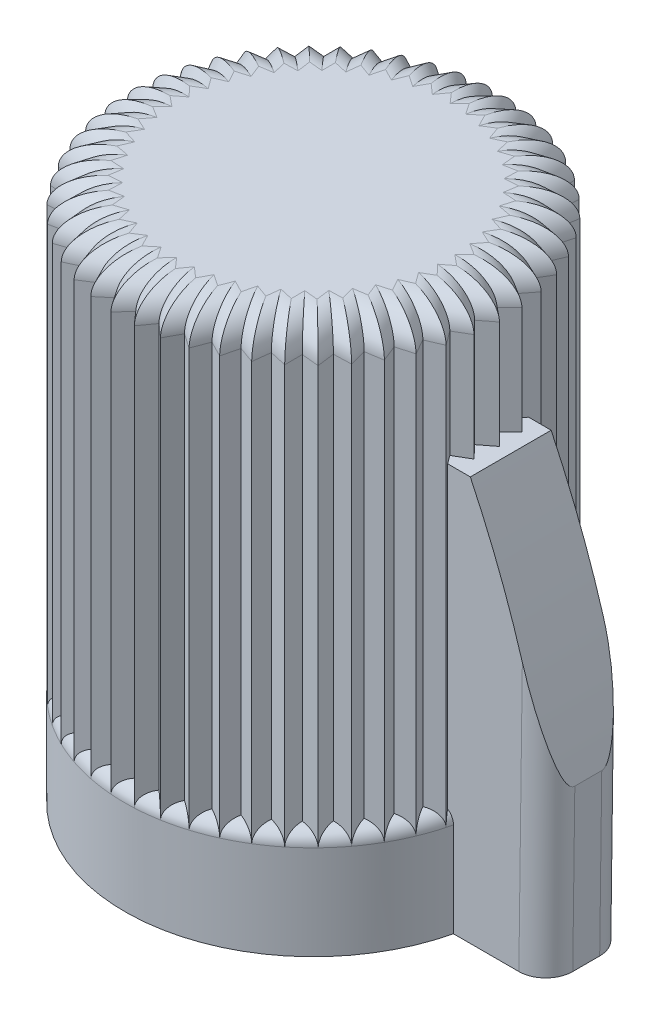
SolidWorks part; units mm, degrees
ref_plane "Спереди" through (0, 0, 0) normal (0, 0, 1) x (1, 0, 0)
ref_plane "Сверху" through (0, 0, 0) normal (0, 1, 0) x (1, 0, 0)
ref_plane "Справа" through (0, 0, 0) normal (1, 0, 0) x (0, 0, -1)
sketch "Sketch1" plane through (0, 0, 0) normal (0, 1, 0) x (1, 0, 0)
  circle A0 centre (0, 0) radius 7
  dimension "D1" = 14
extrude "Boss-Extrude1" add sketch "Sketch1" along normal blind 20
sketch "Sketch2" plane through (0, 0, 0) normal (0, -1, 0) x (1, 0, 0)
  circle A0 centre (0, 0) radius 3.125
  dimension "D1" = 6.25
extrude "Cut-Extrude1" cut sketch "Sketch2" against normal blind 17
sketch "Sketch3" plane through (0, 0, 0) normal (0, -1, 0) x (1, 0, 0)
  circle A0 centre (0, 0) radius 6
  dimension "D1" = 12
extrude "Cut-Extrude2" cut sketch "Sketch3" against normal blind 4
sketch "Sketch4" plane through (0, 20, 0) normal (0, 1, 0) x (1, 0, 0)
  line L0 (6.3681, -1.303) -> (6.7563, -1.8311)
  line L1 (6.7563, -1.8311) -> (6.1545, -2.0909)
  line L2 (6.1545, -2.0909) -> (6.4735, -2.6634)
  line L3 (6.4735, -2.6634) -> (5.8439, -2.8458)
  line L4 (5.8439, -2.8458) -> (6.0886, -3.4538)
  line L5 (6.0886, -3.4538) -> (5.4412, -3.5558)
  line L6 (5.4412, -3.5558) -> (5.6077, -4.1897)
  line L7 (5.6077, -4.1897) -> (4.9526, -4.2097)
  line L8 (4.9526, -4.2097) -> (5.0384, -4.8595)
  line L9 (5.0384, -4.8595) -> (4.386, -4.7972)
  line L10 (4.386, -4.7972) -> (4.3896, -5.4526)
  line L11 (4.3896, -5.4526) -> (3.7501, -5.3091)
  line L12 (3.7501, -5.3091) -> (3.6716, -5.9598)
  line L13 (3.6716, -5.9598) -> (3.0552, -5.7372)
  line L14 (3.0552, -5.7372) -> (2.8957, -6.373)
  line L15 (2.8957, -6.373) -> (2.312, -6.0749)
  line L16 (2.312, -6.0749) -> (2.0741, -6.6857)
  line L17 (2.0741, -6.6857) -> (1.5324, -6.3168)
  line L18 (1.5324, -6.3168) -> (1.2199, -6.8929)
  line L19 (1.2199, -6.8929) -> (0.7286, -6.459)
  line L20 (0.7286, -6.459) -> (0.3463, -6.9914)
  line L21 (0.3463, -6.9914) -> (-0.0867, -6.4994)
  line L22 (-0.0867, -6.4994) -> (-0.5327, -6.9797)
  line L23 (-0.5327, -6.9797) -> (-0.9006, -6.4373)
  line L24 (-0.9006, -6.4373) -> (-1.4033, -6.8579)
  line L25 (-1.4033, -6.8579) -> (-1.7003, -6.2737)
  line L26 (-1.7003, -6.2737) -> (-2.2517, -6.628)
  line L27 (-2.2517, -6.628) -> (-2.4732, -6.0111)
  line L28 (-2.4732, -6.0111) -> (-3.0647, -6.2935)
  line L29 (-3.0647, -6.2935) -> (-3.2071, -5.6537)
  line L30 (-3.2071, -5.6537) -> (-3.8293, -5.8597)
  line L31 (-3.8293, -5.8597) -> (-3.8904, -5.2072)
  line L32 (-3.8904, -5.2072) -> (-4.5335, -5.3336)
  line L33 (-4.5335, -5.3336) -> (-4.5124, -4.6785)
  line L34 (-4.5124, -4.6785) -> (-5.1662, -4.7234)
  line L35 (-5.1662, -4.7234) -> (-5.0631, -4.0761)
  line L36 (-5.0631, -4.0761) -> (-5.7175, -4.0386)
  line L37 (-5.7175, -4.0386) -> (-5.5341, -3.4094)
  line L38 (-5.5341, -3.4094) -> (-6.1786, -3.2902)
  line L39 (-6.1786, -3.2902) -> (-5.9178, -2.6889)
  line L40 (-5.9178, -2.6889) -> (-6.5422, -2.4898)
  line L41 (-6.5422, -2.4898) -> (-6.2081, -1.926)
  line L42 (-6.2081, -1.926) -> (-6.8027, -1.6503)
  line L43 (-6.8027, -1.6503) -> (-6.4005, -1.1327)
  line L44 (-6.4005, -1.1327) -> (-6.9559, -0.7846)
  line L45 (-6.9559, -0.7846) -> (-6.492, -0.3216)
  line L46 (-6.492, -0.3216) -> (-6.9994, 0.0934)
  line L47 (-6.9994, 0.0934) -> (-6.4812, 0.4946)
  line L48 (-6.4812, 0.4946) -> (-6.9325, 0.9699)
  line L49 (-6.9325, 0.9699) -> (-6.3681, 1.303)
  line L50 (-6.3681, 1.303) -> (-6.7563, 1.8311)
  line L51 (-6.7563, 1.8311) -> (-6.1545, 2.0909)
  line L52 (-6.1545, 2.0909) -> (-6.4735, 2.6634)
  line L53 (-6.4735, 2.6634) -> (-5.8439, 2.8458)
  line L54 (-5.8439, 2.8458) -> (-6.0886, 3.4538)
  line L55 (-6.0886, 3.4538) -> (-5.4412, 3.5558)
  line L56 (-5.4412, 3.5558) -> (-5.6077, 4.1897)
  line L57 (-5.6077, 4.1897) -> (-4.9526, 4.2097)
  line L58 (-4.9526, 4.2097) -> (-5.0384, 4.8595)
  line L59 (-5.0384, 4.8595) -> (-4.386, 4.7972)
  line L60 (-4.386, 4.7972) -> (-4.3896, 5.4526)
  line L61 (-4.3896, 5.4526) -> (-3.7501, 5.3091)
  line L62 (-3.7501, 5.3091) -> (-3.6716, 5.9598)
  line L63 (-3.6716, 5.9598) -> (-3.0552, 5.7372)
  line L64 (-3.0552, 5.7372) -> (-2.8957, 6.373)
  line L65 (-2.8957, 6.373) -> (-2.312, 6.0749)
  line L66 (-2.312, 6.0749) -> (-2.0741, 6.6857)
  line L67 (-2.0741, 6.6857) -> (-1.5324, 6.3168)
  line L68 (-1.5324, 6.3168) -> (-1.2199, 6.8929)
  line L69 (-1.2199, 6.8929) -> (-0.7286, 6.459)
  line L70 (-0.7286, 6.459) -> (-0.3463, 6.9914)
  line L71 (-0.3463, 6.9914) -> (0.0867, 6.4994)
  line L72 (0.0867, 6.4994) -> (0.5327, 6.9797)
  line L73 (0.5327, 6.9797) -> (0.9006, 6.4373)
  line L74 (0.9006, 6.4373) -> (1.4033, 6.8579)
  line L75 (1.4033, 6.8579) -> (1.7003, 6.2737)
  line L76 (1.7003, 6.2737) -> (2.2517, 6.628)
  line L77 (2.2517, 6.628) -> (2.4732, 6.0111)
  line L78 (2.4732, 6.0111) -> (3.0647, 6.2935)
  line L79 (3.0647, 6.2935) -> (3.2071, 5.6537)
  line L80 (3.2071, 5.6537) -> (3.8293, 5.8597)
  line L81 (3.8293, 5.8597) -> (3.8904, 5.2072)
  line L82 (3.8904, 5.2072) -> (4.5335, 5.3336)
  line L83 (4.5335, 5.3336) -> (4.5124, 4.6785)
  line L84 (4.5124, 4.6785) -> (5.1662, 4.7234)
  line L85 (5.1662, 4.7234) -> (5.0631, 4.0761)
  line L86 (5.0631, 4.0761) -> (5.7175, 4.0386)
  line L87 (5.7175, 4.0386) -> (5.5341, 3.4094)
  line L88 (5.5341, 3.4094) -> (6.1786, 3.2902)
  line L89 (6.1786, 3.2902) -> (5.9178, 2.6889)
  line L90 (5.9178, 2.6889) -> (6.5422, 2.4898)
  line L91 (6.5422, 2.4898) -> (6.2081, 1.926)
  line L92 (6.2081, 1.926) -> (6.8027, 1.6503)
  line L93 (6.8027, 1.6503) -> (6.4005, 1.1327)
  line L94 (6.4005, 1.1327) -> (6.9559, 0.7846)
  line L95 (6.9559, 0.7846) -> (6.492, 0.3216)
  line L96 (6.492, 0.3216) -> (6.9994, -0.0934)
  line L97 (6.9994, -0.0934) -> (6.4812, -0.4946)
  line L98 (6.4812, -0.4946) -> (6.9325, -0.9699)
  line L99 (6.9325, -0.9699) -> (6.3681, -1.303)
  circle A0 centre (0, 0) radius 6.5 construction
  circle A1 centre (0, 0) radius 7 construction
  point P158 (0, 0)
  dimension "D1" = 0.5
  dimension "D2" = 50
extrude "Cut-Extrude4" cut sketch "Sketch4" against normal blind 16 flip side to cut
fillet "Fillet1" radius 0.5 50 edges at (6.9797, 4, 0.5327) (6.8579, 4, 1.4033) (6.628, 4, 2.2517) (6.2935, 4, 3.0647) (5.8597, 4, 3.8293) (5.3336, 4, 4.5335) (4.7234, 4, 5.1662) (4.0386, 4, 5.7175) (3.2902, 4, 6.1786) (2.4898, 4, 6.5422) (1.6503, 4, 6.8027) (0.7846, 4, 6.9559) (-0.0934, 4, 6.9994) (-0.9699, 4, 6.9325) (-1.8311, 4, 6.7563) (-2.6634, 4, 6.4735) (-3.4538, 4, 6.0886) (-4.1897, 4, 5.6077) (-4.8595, 4, 5.0384) (-5.4526, 4, 4.3896) (-5.9598, 4, 3.6716) (-6.373, 4, 2.8957) (-6.6857, 4, 2.0741) (-6.8929, 4, 1.2199) (-6.9914, 4, 0.3463) (-6.9797, 4, -0.5327) (-6.8579, 4, -1.4033) (-6.628, 4, -2.2517) (-6.2935, 4, -3.0647) (-5.8597, 4, -3.8293) (-5.3336, 4, -4.5335) (-4.7234, 4, -5.1662) (-4.0386, 4, -5.7175) (-3.2902, 4, -6.1786) (-2.4898, 4, -6.5422) (-1.6503, 4, -6.8027) (-0.7846, 4, -6.9559) (0.0934, 4, -6.9994) (0.9699, 4, -6.9325) (1.8311, 4, -6.7563) (2.6634, 4, -6.4735) (3.4538, 4, -6.0886) (4.1897, 4, -5.6077) (4.8595, 4, -5.0384) (5.4526, 4, -4.3896) (5.9598, 4, -3.6716) (6.373, 4, -2.8957) (6.6857, 4, -2.0741) (6.8929, 4, -1.2199) (6.9914, 4, -0.3463)
fillet "Fillet2" radius 1 100 edges at (6.4554, 20, 1.961) (6.314, 20, 2.3772) (6.1587, 20, 2.7546) (5.9663, 20, 3.1498) (5.7649, 20, 3.5048) (5.5245, 20, 3.8727) (5.2802, 20, 4.1997) (4.9955, 20, 4.5346) (4.7122, 20, 4.8283) (4.3878, 20, 5.1249) (4.0699, 20, 5.3809) (3.7109, 20, 5.6344) (3.3634, 20, 5.8485) (2.9754, 20, 6.0551) (2.6039, 20, 6.2239) (2.1931, 20, 6.3803) (1.8033, 20, 6.5012) (1.3761, 20, 6.6048) (0.9742, 20, 6.676) (0.5375, 20, 6.7252) (0.1298, 20, 6.7454) (-0.3097, 20, 6.7396) (-0.7166, 20, 6.7085) (-1.1519, 20, 6.6476) (-1.5518, 20, 6.5658) (-1.976, 20, 6.4508) (-2.3625, 20, 6.3195) (-2.7689, 20, 6.1523) (-3.1359, 20, 5.9736) (-3.5182, 20, 5.7567) (-3.8598, 20, 5.5335) (-4.2119, 20, 5.2704) (-4.5229, 20, 5.0061) (-4.8393, 20, 4.7009) (-5.1147, 20, 4.3997) (-5.3903, 20, 4.0574) (-5.6258, 20, 3.724) (-5.8563, 20, 3.3498) (-6.0482, 20, 2.9895) (-6.23, 20, 2.5894) (-6.3752, 20, 2.2079) (-6.5054, 20, 1.7881) (-6.6016, 20, 1.3915) (-6.6782, 20, 0.9587) (-6.724, 20, 0.5531) (-6.7457, 20, 0.1141) (-6.7403, 20, -0.294) (-6.7068, 20, -0.7322) (-6.6503, 20, -1.1364) (-6.5622, 20, -1.5671) (-6.4554, 20, -1.961) (-6.314, 20, -2.3772) (-6.1587, 20, -2.7546) (-5.9663, 20, -3.1498) (-5.7649, 20, -3.5048) (-5.5245, 20, -3.8727) (-5.2802, 20, -4.1997) (-4.9955, 20, -4.5346) (-4.7122, 20, -4.8283) (-4.3878, 20, -5.1249) (-4.0699, 20, -5.3809) (-3.7109, 20, -5.6344) (-3.3634, 20, -5.8485) (-2.9754, 20, -6.0551) (-2.6039, 20, -6.2239) (-2.1931, 20, -6.3803) (-1.8033, 20, -6.5012) (-1.3761, 20, -6.6048) (-0.9742, 20, -6.676) (-0.5375, 20, -6.7252) (-0.1298, 20, -6.7454) (0.3097, 20, -6.7396) (0.7166, 20, -6.7085) (1.1519, 20, -6.6476) (1.5518, 20, -6.5658) (1.976, 20, -6.4508) (2.3625, 20, -6.3195) (2.7689, 20, -6.1523) (3.1359, 20, -5.9736) (3.5182, 20, -5.7567) (3.8598, 20, -5.5335) (4.2119, 20, -5.2704) (4.5229, 20, -5.0061) (4.8393, 20, -4.7009) (5.1147, 20, -4.3997) (5.3903, 20, -4.0574) (5.6258, 20, -3.724) (5.8563, 20, -3.3498) (6.0482, 20, -2.9895) (6.23, 20, -2.5894) (6.3752, 20, -2.2079) (6.5054, 20, -1.7881) (6.6016, 20, -1.3915) (6.6782, 20, -0.9587) (6.724, 20, -0.5531) (6.7457, 20, -0.1141) (6.7403, 20, 0.294) (6.7068, 20, 0.7322) (6.6503, 20, 1.1364) (6.5622, 20, 1.5671)
sketch "Sketch5" plane through (0, 0, 0) normal (0, -1, 0) x (1, 0, 0)
  line L0 (0, 0) -> (15.1541, 0.2021) construction
  line L2 (10.8371, 1.6112) -> (5.8371, 1.6112)
  line L3 (10.8371, 1.6112) -> (10.8371, -1.3888)
  line L4 (10.8371, -1.3888) -> (5.8371, -1.3888)
  line L5 (5.8371, 1.6112) -> (5.8371, -1.3888)
  line L6 (10.8371, 1.6112) -> (5.8371, -1.3888) construction
  line L7 (10.8371, -1.3888) -> (5.8371, 1.6112) construction
  circle A0 centre (0, 0) radius 6 construction
  point P3 (8.3371, 0.1112)
  dimension "D1" = 5
  dimension "D2" = 3
extrude "Boss-Extrude2" add sketch "Sketch5" against normal offset from surface (15 mm away) 5 up to face at (0, 20, 0)
sketch "Sketch6" plane through (0, 0, -1.3888) normal (0, 0, -1) x (-1, 0, 0)
  line L0 (-6.5995, 15) -> (-10.8371, 15) construction
  line L1 (-10.8371, 15) -> (-10.8371, 0) construction
  arc A0 (-10.8371, 0) -> (-7.4371, 15) centre (23.9512, 0) cw
  arc A1 (-7.4371, 15) -> (-10.8371, 0) centre (-14.7625, 8.7751) ccw
  dimension "D1" = 3.4
extrude "Cut-Extrude5" cut sketch "Sketch6" against normal through all
sketch "Sketch7" plane through (0, 0, -1.3888) normal (0, 0, -1) x (-1, 0, 0)
  line L0 (-10.2387, 0) -> (-10.3157, 6)
  line L1 (-6.8608, 0) -> (-10.8371, 0) construction
  arc A0 (-7.4371, 15) -> (-10.8371, 0) centre (23.9512, 0) ccw construction
  arc A1 (-10.2387, 0) -> (-10.3157, 6) centre (-15.2711, 2.9359) cw
  dimension "D1" = 6
extrude "Cut-Extrude6" cut sketch "Sketch7" against normal through all
fillet "Fillet10" radius 1 2 edges at (10.2772, 3, 1.6112) (10.2772, 3, -1.3888)
